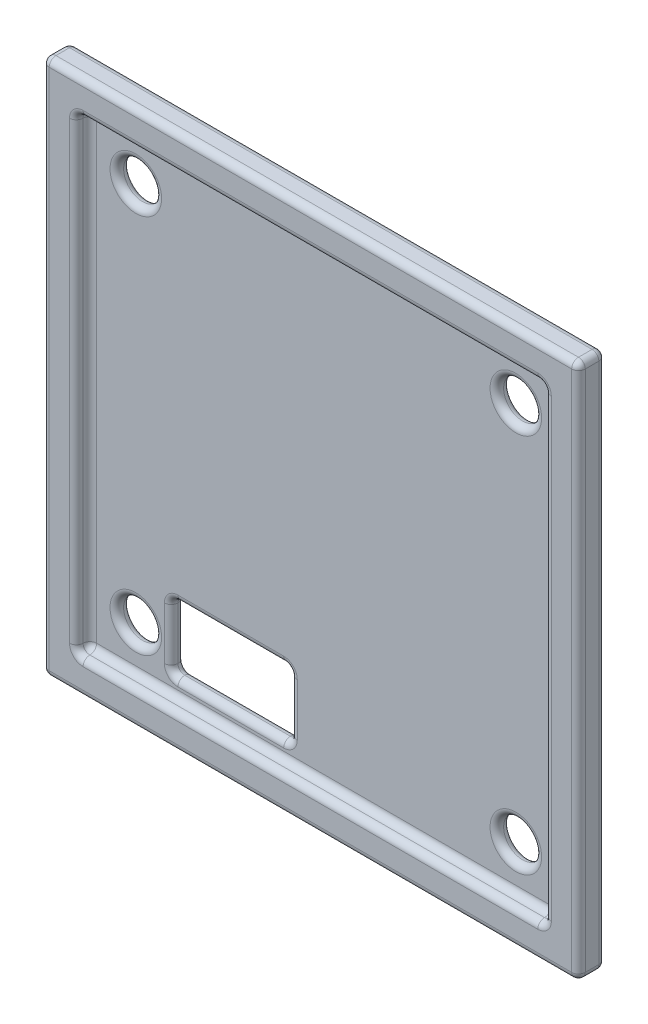
SolidWorks part; units mm, degrees
ref_plane "Front Plane" through (0, 0, 0) normal (0, 0, 1) x (1, 0, 0)
ref_plane "Top Plane" through (0, 0, 0) normal (0, 1, 0) x (1, 0, 0)
ref_plane "Right Plane" through (0, 0, 0) normal (1, 0, 0) x (0, 0, -1)
sketch "Sketch1" plane through (0, 0, 0) normal (0, 0, 1) x (1, 0, 0)
  line L1 (-19.75, 19.75) -> (19.75, 19.75)
  line L2 (-19.75, 19.75) -> (-19.75, -19.75)
  line L3 (-19.75, -19.75) -> (19.75, -19.75)
  line L4 (19.75, 19.75) -> (19.75, -19.75)
  line L5 (-19.75, 19.75) -> (19.75, -19.75) construction
  line L6 (-19.75, -19.75) -> (19.75, 19.75) construction
  point P0 (0, 0)
  dimension "D1" = 39.5
  dimension "D2" = 39.5
extrude "Boss-Extrude1" add sketch "Sketch1" along normal blind 1
sketch "Sketch2" plane through (0, 0, 1) normal (0, 0, 1) x (1, 0, 0)
  line L1 (-19.75, 19.75) -> (19.75, 19.75)
  line L2 (-19.75, 19.75) -> (-19.75, -19.75)
  line L3 (-19.75, -19.75) -> (19.75, -19.75)
  line L4 (19.75, 19.75) -> (19.75, -19.75)
  line L5 (-17.25, 17.25) -> (17.25, 17.25)
  line L6 (-17.25, 17.25) -> (-17.25, -17.25)
  line L7 (-17.25, -17.25) -> (17.25, -17.25)
  line L8 (17.25, 17.25) -> (17.25, -17.25)
  point P11 (-16.9031, 16.6675)
  point P12 (-16.9693, 17.0805)
  dimension "D1" = 2.5
  dimension "D2" = 2.5
  dimension "D3" = 2.5
  dimension "D4" = 2.5
extrude "Boss-Extrude2" add sketch "Sketch2" along normal blind 1
sketch "Sketch3" plane through (0, 0, 0) normal (0, 0, -1) x (-1, 0, 0)
  line L1 (2.4693, -11.1805) -> (11.261, -11.1805)
  line L2 (2.4693, -11.1805) -> (2.4693, -16.0452)
  line L3 (2.4693, -16.0452) -> (11.261, -16.0452)
  line L4 (11.261, -11.1805) -> (11.261, -16.0452)
  circle A0 centre (-14.1346, 14.0198) radius 1.4
  circle A1 centre (13.8654, 14.0198) radius 1.4
  circle A2 centre (13.8654, -13.9802) radius 1.4
  circle A3 centre (-14.1346, -13.9802) radius 1.4
  dimension "D1" = 2
  dimension "D2" = 2
extrude "Cut-Extrude1" cut sketch "Sketch3" against normal blind 2
fillet "Fillet1" radius 0.5 36 edges at (12.7346, -13.9802, 0) (-15.2654, -13.9802, 0) (-15.2654, 14.0198, 0) (12.7346, 14.0198, 0) (-2.4693, -13.6128, 0) (-6.8652, -16.0452, 0) (-11.261, -13.6128, 0) (-6.8652, -11.1805, 0) (15.5346, 14.0198, 1) (-12.4654, 14.0198, 1) (-12.4654, -13.9802, 1) (15.5346, -13.9802, 1) (-17.25, 0, 1) (0, -17.25, 1) (17.25, 0, 1) (0, 17.25, 1) (-17.25, 0, 2) (0, -17.25, 2) (17.25, 0, 2) (0, 17.25, 2) (-19.75, 0, 2) (0, -19.75, 2) (19.75, 0, 2) (0, 19.75, 2) (19.75, 0, 0) (0, 19.75, 0) (-19.75, 0, 0) (0, -19.75, 0) (19.75, -19.75, 1) (-19.75, -19.75, 1) (-19.75, 19.75, 1) (19.75, 19.75, 1) (-6.8652, -16.0452, 1) (-11.261, -13.6128, 1) (-6.8652, -11.1805, 1) (-2.4693, -13.6128, 1)
